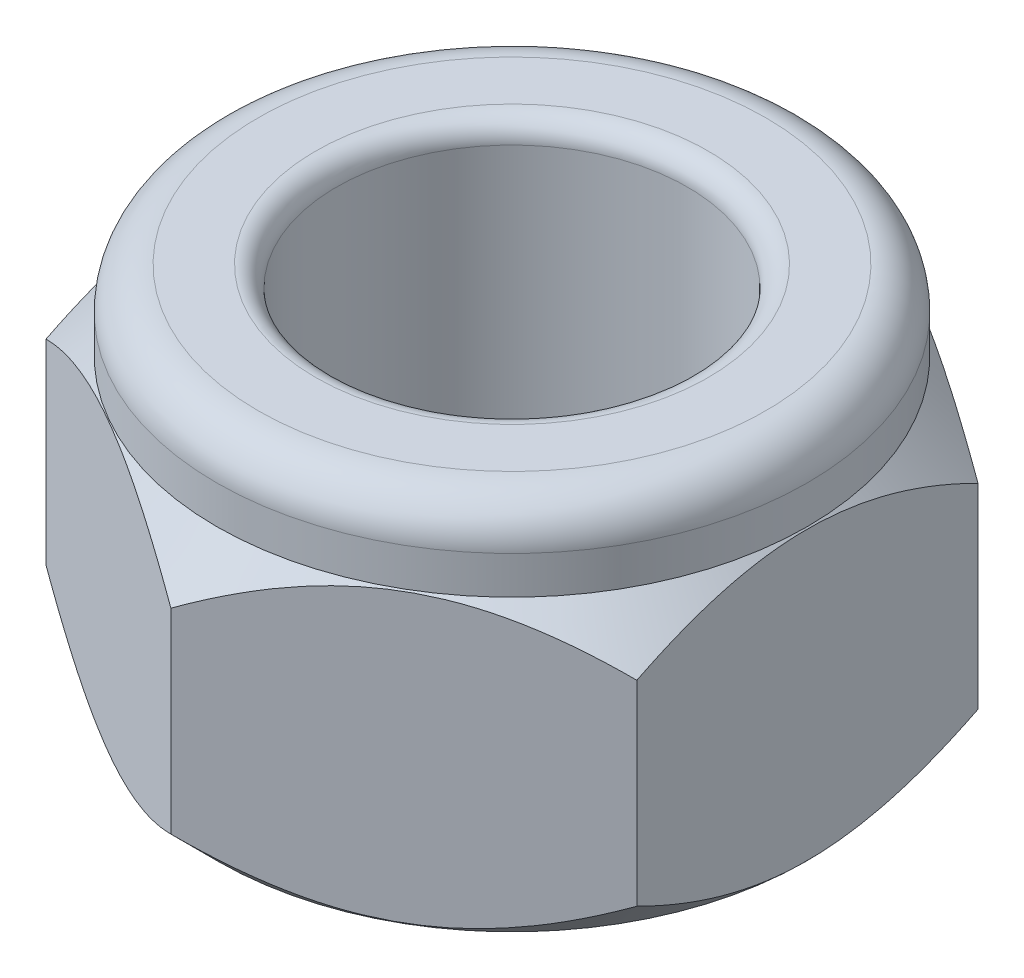
SolidWorks part; units mm, degrees
material "1023 Carbon Steel Sheet (SS)"
ref_plane "Front" through (0, 0, 0) normal (0, 0, 1) x (1, 0, 0)
ref_plane "Top" through (0, 0, 0) normal (0, 1, 0) x (1, 0, 0)
ref_plane "Right" through (0, 0, 0) normal (1, 0, 0) x (0, 0, -1)
sketch "Sketch1" plane through (0, 0, 0) normal (0, 1, 0) x (1, 0, 0)
  line L0 (0, 0) -> (0, -50000) construction
  line L2 (0, 8.1984) -> (-7.1, 4.0992)
  line L3 (-7.1, 4.0992) -> (-7.1, -4.0992)
  line L4 (-7.1, -4.0992) -> (0, -8.1984)
  line L5 (0, -8.1984) -> (7.1, -4.0992)
  line L6 (7.1, -4.0992) -> (7.1, 4.0992)
  line L7 (7.1, 4.0992) -> (0, 8.1984)
  circle A0 centre (0, 0) radius 4
  circle A1 centre (0, 0) radius 7.1 construction
  dimension "D1" = 8
  dimension "D2" = 14.2
extrude "Boss-Extrude1" add sketch "Sketch1" along normal blind 7
hole_wizard "3/8-24 Tapped Hole6" positions "3DSketch2" profile "Sketch3" tap size "3/8-24" standard "ANSI Inch"
sketch3d "3DSketch2"
  line L0 (0, 7, 0) -> (0, 0, 0) construction
  point P0 (0, 7, 0)
sketch "Sketch3" plane through (0, 7, 0) normal (1, 0, 0) x (0, 0, 1)
  line L0 (0, 0) -> (0, 17.8335)
  line L1 (0, 17.8335) -> (4.2164, 15.3)
  line L2 (4.2164, 15.3) -> (4.2164, 0)
  line L5 (4.2164, 0) -> (0, 0)
  line L10 (0, 17.8335) -> (-4.2164, 15.3) construction
  line L11 (0, -6.35) -> (0, 107.95) construction
  dimension "Tap Drill Dia." = 8.4328
  dimension "Tap Drill Depth" = 15.3
  dimension "Drill Angle" = 118
cosmetic thread "Hole Thread4" parameters "D1"=9.41, "D2"=9.525
sketch "Sketch8" plane through (0, 0, 0) normal (0, 0, 1) x (1, 0, 0)
  line L0 (-6.55, -0.5) -> (-8.05, -0.5)
  line L1 (-8.05, -0.5) -> (-8.05, 1) construction
  line L2 (-8.05, 1) -> (-6.55, -0.5) construction
  line L3 (-7.1, 7) -> (-7.1, 0) construction
  line L4 (0, 0) -> (-7.1, 0) construction
  line L5 (0, 0) -> (0, 10.0901) construction
  line L6 (-8.05, 1) -> (-11.05, 1) construction
  line L7 (-11.05, 1) -> (-11.05, -0.5)
  line L8 (-11.05, -0.5) -> (-8.05, -0.5)
  line L9 (-6.55, -0.5) -> (-8.55, 1.5)
  line L10 (-8.55, 1.5) -> (-11.05, 1.5)
  line L11 (-11.05, 1.5) -> (-11.05, 1)
  line L12 (7.1, 3.5) -> (-7.1, 3.5) construction
  line L13 (7.1, 7) -> (7.1, 0) construction
  line L14 (-8.05, 6) -> (-11.05, 6) construction
  line L15 (-8.05, 6) -> (-6.55, 7.5) construction
  line L16 (-8.05, 7.5) -> (-8.05, 6) construction
  line L17 (-11.05, 5.5) -> (-11.05, 6)
  line L18 (-8.55, 5.5) -> (-11.05, 5.5)
  line L19 (-6.55, 7.5) -> (-8.55, 5.5)
  line L20 (-11.05, 7.5) -> (-8.05, 7.5)
  line L21 (-11.05, 6) -> (-11.05, 7.5)
  line L22 (-6.55, 7.5) -> (-8.05, 7.5)
  dimension "D1" = 1.5
  dimension "D2" = 45
  dimension "D3" = 0.95
  dimension "D4" = 0.5
  dimension "D5" = 3
  dimension "D6" = 2
revolve "Cut-Revolve4" cut sketch "Sketch8" angle 360 about L5
sketch "Sketch9" plane through (0, 7, 0) normal (0, 1, 0) x (1, 0, 0)
  line L0 (7.1, 4.0992) -> (0, 8.1984) construction
  circle A0 centre (0, 0) radius 7.1
  circle A1 centre (0, 0) radius 4.2164
  circle A2 centre (0, 0) radius 4.2164 construction
extrude "Boss-Extrude3" add sketch "Sketch9" along normal blind 1.91
fillet "Fillet3" radius 1 1 edges at (0, 8.91, 7.1)
fillet "Fillet4" radius 0.5 1 edges at (0, 8.91, 4.2164)
